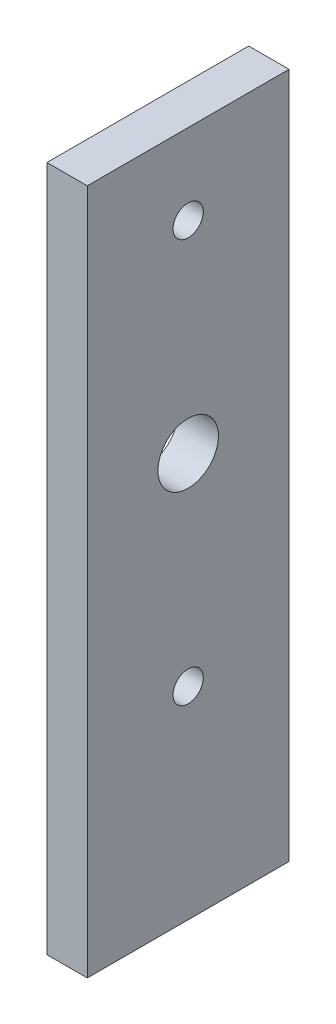
SolidWorks part; units mm, degrees
ref_plane "Front Plane" through (0, 0, 0) normal (0, 0, 1) x (1, 0, 0)
ref_plane "Top Plane" through (0, 0, 0) normal (0, 1, 0) x (1, 0, 0)
ref_plane "Right Plane" through (0, 0, 0) normal (1, 0, 0) x (0, 0, -1)
sketch "Sketch1" plane through (0, 0, 0) normal (0, 1, 0) x (1, 0, 0)
  line L0 (0, 0) -> (10, 0)
  line L1 (10, 0) -> (10, 50)
  line L2 (0, 0) -> (0, 50)
  line L3 (0, 50) -> (10, 50)
  dimension "D1" = 50
  dimension "D2" = 10
extrude "Boss-Extrude1" add sketch "Sketch1" along normal blind 170
sketch "Sketch2" plane through (10, 0, 0) normal (1, 0, 0) x (0, 0, -1)
  circle A0 centre (25, 50.0962) radius 3.75
  circle A1 centre (25, 150.0962) radius 3.75
  circle A2 centre (25, 100.0962) radius 7.5
extrude "Cut-Extrude1" cut sketch "Sketch2" against normal blind 10
